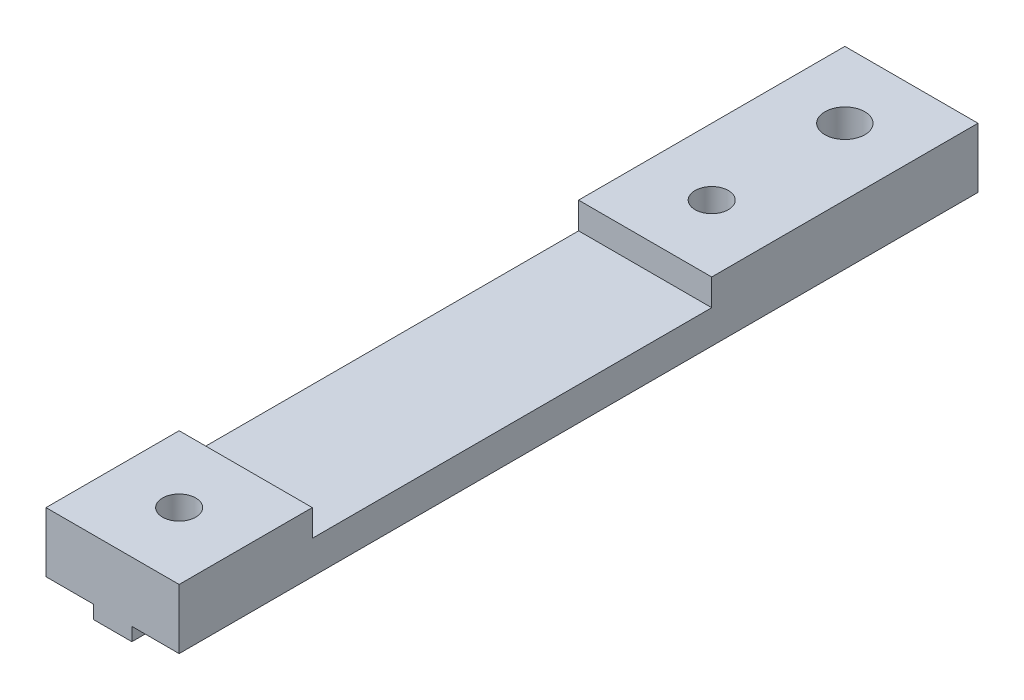
SolidWorks part; units mm, degrees
ref_plane "Front Plane" through (0, 0, 0) normal (0, 0, 1) x (1, 0, 0)
ref_plane "Top Plane" through (0, 0, 0) normal (0, 1, 0) x (1, 0, 0)
ref_plane "Right Plane" through (0, 0, 0) normal (1, 0, 0) x (0, 0, -1)
sketch "Sketch1" plane through (0, 0, 0) normal (0, 0, 1) x (1, 0, 0)
  line L0 (-5, 0) -> (5, 0)
  line L1 (5, 0) -> (5, -4.5)
  line L2 (5, -4.5) -> (1.45, -4.5)
  line L3 (1.45, -4.5) -> (1.45, -5.5)
  line L4 (1.45, -5.5) -> (-1.45, -5.5)
  line L5 (-1.45, -5.5) -> (-1.45, -4.5)
  line L6 (-1.45, -4.5) -> (-5, -4.5)
  line L7 (-5, -4.5) -> (-5, 0)
  point P9 (0, 0)
  dimension "D1" = 10
  dimension "D2" = 4.5
  dimension "D3" = 1
  dimension "D4" = 2.9
extrude "Main" add sketch "Sketch1" along normal blind 60
sketch "Sketch2" plane through (0, 0, 0) normal (0, 1, 0) x (1, 0, 0)
  line L0 (5, -60) -> (-5, -60) construction
  line L1 (5, 0) -> (-5, 0) construction
  circle A0 centre (0, -55) radius 1.25
  circle A1 centre (0, -15) radius 1.25
  circle A2 centre (0, -5) radius 1.5
  point P9 (0, -13.9741)
  dimension "D1" = 2.5
  dimension "D4" = 3
  dimension "D2" = 5
  dimension "D3" = 40
  dimension "D5" = 5
extrude "I2CBoardFixHole" cut sketch "Sketch2" against normal through all
sketch "Sketch3" plane through (0, 0, 0) normal (0, 1, 0) x (1, 0, 0)
  line L1 (-5, -60) -> (-5, 0) construction
  line L5 (5, -60) -> (5, 0) construction
  line L6 (-5, -20) -> (5, -20)
  line L7 (-5, -20) -> (-5, -50)
  line L8 (-5, -50) -> (5, -50)
  line L9 (5, -20) -> (5, -50)
  line L10 (5, -60) -> (-5, -60) construction
  point P0 (-5, -20)
  dimension "D2" = 30
  dimension "D3" = 10
extrude "Pins" cut sketch "Sketch3" against normal blind 2
